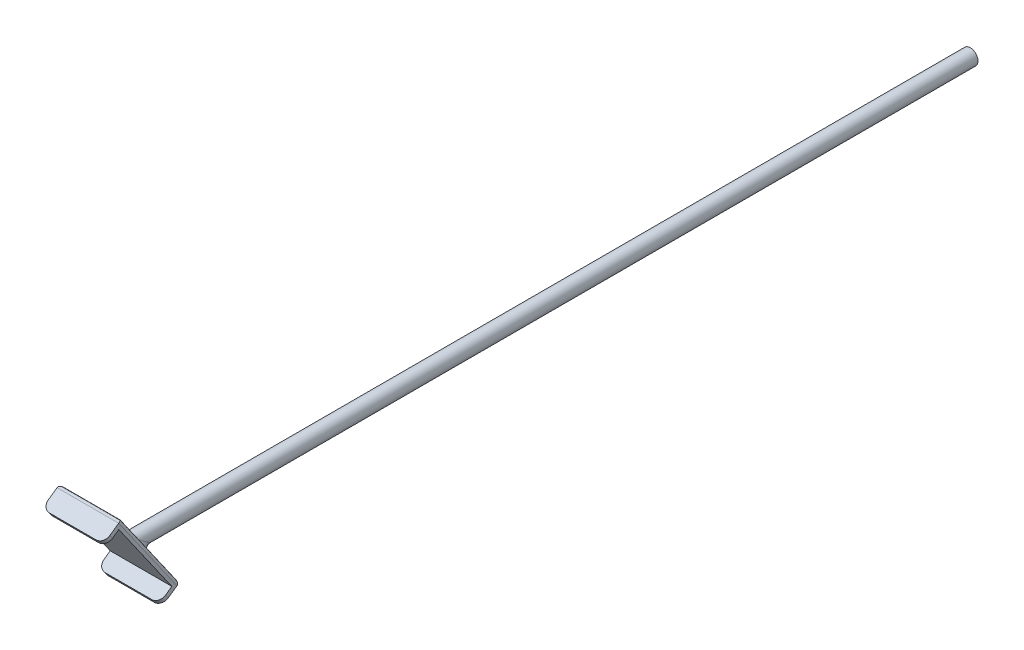
SolidWorks part; units mm, degrees
material "6061 Alloy"
ref_plane "Front Plane" through (0, 0, 0) normal (0, 0, 1) x (1, 0, 0)
ref_plane "Top Plane" through (0, 0, 0) normal (0, 1, 0) x (1, 0, 0)
ref_plane "Right Plane" through (0, 0, 0) normal (1, 0, 0) x (0, 0, -1)
sketch "Sketch1" plane through (0, 0, 0) normal (0, 0, 1) x (1, 0, 0)
  circle A0 centre (0, 0) radius 5
  dimension "D1" = 10
extrude "Boss-Extrude1" add sketch "Sketch1" along normal blind 550
sketch "Sketch2" plane through (0, 0, 0) normal (1, 0, 0) x (0, 0, -1)
  line L4 (-553.501, 10) -> (-553.501, -10)
  line L5 (-553.501, -10) -> (-539.4969, -10)
  line L6 (-539.4969, -10) -> (-553.501, 10)
  line L8 (-553.501, 0) -> (0, 0) construction
  point P3 (-570, -10)
  dimension "D1" = 20
  dimension "D2" = 35
extrude "Cut-Extrude1" cut sketch "Sketch2" against normal through all both and the other way through all
sketch "Sketch3" plane through (0, -256.7705, 366.7063) normal (0, -0.5736, 0.8192) x (1, 0, 0)
  line L0 (-5, 313.4589) -> (5, 313.4589) construction
  line L1 (0, 353.4589) -> (0, 330.4589) construction
  line L2 (-20, 353.4589) -> (20, 353.4589)
  line L3 (-20, 353.4589) -> (-20, 293.4589)
  line L4 (-20, 293.4589) -> (20, 293.4589)
  line L5 (20, 353.4589) -> (20, 293.4589)
  line L6 (-20, 353.4589) -> (20, 293.4589) construction
  line L7 (-20, 293.4589) -> (20, 353.4589) construction
  line L8 (0, 323.4589) -> (0, 313.4589) construction
  circle A0 centre (0, 330.4589) radius 2.5
  point P2 (0, 323.4589)
  dimension "D3" = 5
  dimension "D1" = 60
  dimension "D2" = 40
  dimension "D4" = 23
  dimension "D5" = 10
extrude "Boss-Extrude2" add sketch "Sketch3" along normal blind 4
sketch "Sketch4" plane through (0, 289.5366, 202.7357) normal (0, 0.8192, 0.5736) x (1, 0, 0)
  line L0 (-20, -451.6657) -> (-20, -447.6657) construction
  line L1 (20, -447.6657) -> (-20, -447.6657)
  line L2 (20, -447.6657) -> (20, -461.6657)
  line L3 (20, -461.6657) -> (-20, -461.6657)
  line L4 (-20, -447.6657) -> (-20, -461.6657)
  dimension "D1" = 14
extrude "Boss-Extrude3" add sketch "Sketch4" along normal blind 3
sketch "Sketch5" plane through (0, 240.3875, 168.3211) normal (0, -0.8192, -0.5736) x (1, 0, 0)
  line L0 (20, 451.6657) -> (20, 447.6657) construction
  line L1 (-20, 447.6657) -> (20, 447.6657)
  line L2 (-20, 447.6657) -> (-20, 461.6657)
  line L3 (-20, 461.6657) -> (20, 461.6657)
  line L4 (20, 447.6657) -> (20, 461.6657)
  dimension "D1" = 14
extrude "Boss-Extrude4" add sketch "Sketch5" along normal blind 3
fillet "Fillet1" radius 5 4 edges at (-20, -25.6418, 545.6352) (-20, 25.9647, 581.7705) (20, 25.9647, 581.7705) (20, -25.6418, 545.6352)
fillet "Fillet2" radius 5 1 edges at (0, -5, 542.9979)
fillet "Fillet3" radius 2 4 edges at (0, -18.8405, 533.3067) (20, 8.1915, 552.2347) (-20, 8.1915, 552.2347) (0, 35.2235, 571.1627)
